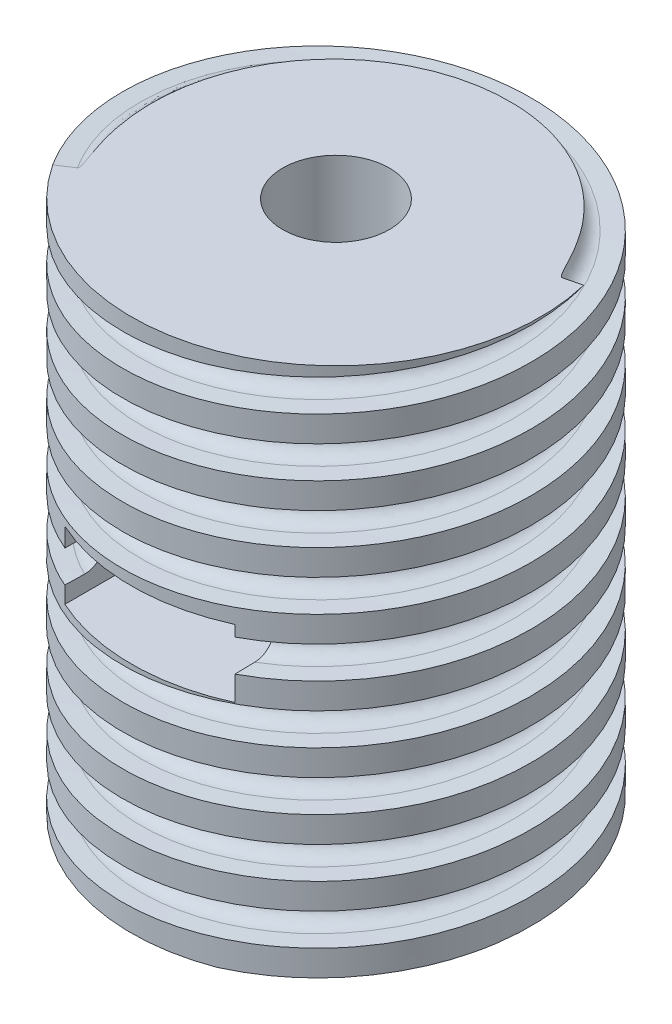
SolidWorks part; units mm, degrees
ref_plane "Front Plane" through (0, 0, 0) normal (0, 0, 1) x (1, 0, 0)
ref_plane "Top Plane" through (0, 0, 0) normal (0, 1, 0) x (1, 0, 0)
ref_plane "Right Plane" through (0, 0, 0) normal (1, 0, 0) x (0, 0, -1)
sketch "Sketch1" plane through (0, 0, 0) normal (0, 1, 0) x (1, 0, 0)
  circle A0 centre (0, 0) radius 11.5
  circle A1 centre (0, 0) radius 1.5
  dimension "D1" = 23
  dimension "D2" = 3
extrude "Boss-Extrude1" add sketch "Sketch1" along normal blind 30
sketch "Sketch3" plane through (0, 0, 0) normal (0, 0, 1) x (1, 0, 0)
  line L1 (-10.5, -1) -> (-20.5, -1)
  line L2 (-20.5, -1) -> (-20.5, -2.8)
  line L3 (-20.5, -2.8) -> (-10.5, -2.8)
  line L4 (0, 0) -> (0, -7.8644) construction
  line L5 (-11.5, 0) -> (11.5, 0) construction
  arc A0 (-10.5, -2.8) -> (-10.5, -1) centre (-10.5, -1.9) ccw
  dimension "D1" = 1.8
  dimension "D2" = 10
  dimension "D3" = 10.5
  dimension "D4" = 1
ref_plane "Plane1" through (0, -5, 0) normal (0, -1, 0) x (-1, 0, 0)
sketch "Sketch6" plane through (0, -5, 0) normal (0, -1, 0) x (1, 0, 0)
  circle A1 centre (0, 0) radius 10
  dimension "D1" = 20
curve "Helix/Spiral1" pitch 3.25 height 65 radius 10 centre (0, -5, 0) axis (0, 1, 0) start towards (0, 0, -1)
sweep "Cut-Sweep1" cut profiles "Sketch3" path "Helix/Spiral1"
ref_plane "Plane2" through (0, 0, 11.5) normal (0, 0, 1) x (1, 0, 0)
sketch "Sketch7" plane through (0, 0, 11.5) normal (0, 0, 1) x (1, 0, 0)
  line L0 (0, 0) -> (0, 30) construction
  line L1 (11.5, 30) -> (-9.6136, 30) construction
  line L3 (4.78, 16.9) -> (-4.78, 16.9)
  line L4 (4.78, 16.9) -> (4.78, 13.1)
  line L5 (4.78, 13.1) -> (-4.78, 13.1)
  line L6 (-4.78, 16.9) -> (-4.78, 13.1)
  line L7 (4.78, 16.9) -> (-4.78, 13.1) construction
  line L8 (4.78, 13.1) -> (-4.78, 16.9) construction
  point P5 (0, 15)
  point P6 (0, 15)
  dimension "D1" = 9.56
  dimension "D2" = 3.8
extrude "Cut-Extrude1" cut sketch "Sketch7" against normal blind 6
sketch "Sketch9" plane through (0, 30, 0) normal (0, 1, 0) x (1, 0, 0)
  circle A0 centre (0, 0) radius 3
  dimension "D1" = 6
extrude "Cut-Extrude5" cut sketch "Sketch9" against normal blind 25
sketch "Sketch8" plane through (0, 0, 5.5) normal (0, 0, 1) x (1, 0, 0)
  line L0 (-4.78, 15) -> (4.78, 15) construction
  line L1 (-4.78, 16.9) -> (-4.78, 13.1) construction
  line L2 (4.78, 13.1) -> (4.78, 16.9) construction
  circle A0 centre (-2.75, 15) radius 1.25
  circle A1 centre (2.75, 15) radius 1.25
  point P6 (0, 15)
  dimension "D1" = 2.5
  dimension "D2" = 2.75
  dimension "D3" = 2.75
extrude "Cut-Extrude6" cut sketch "Sketch8" against normal up to next
